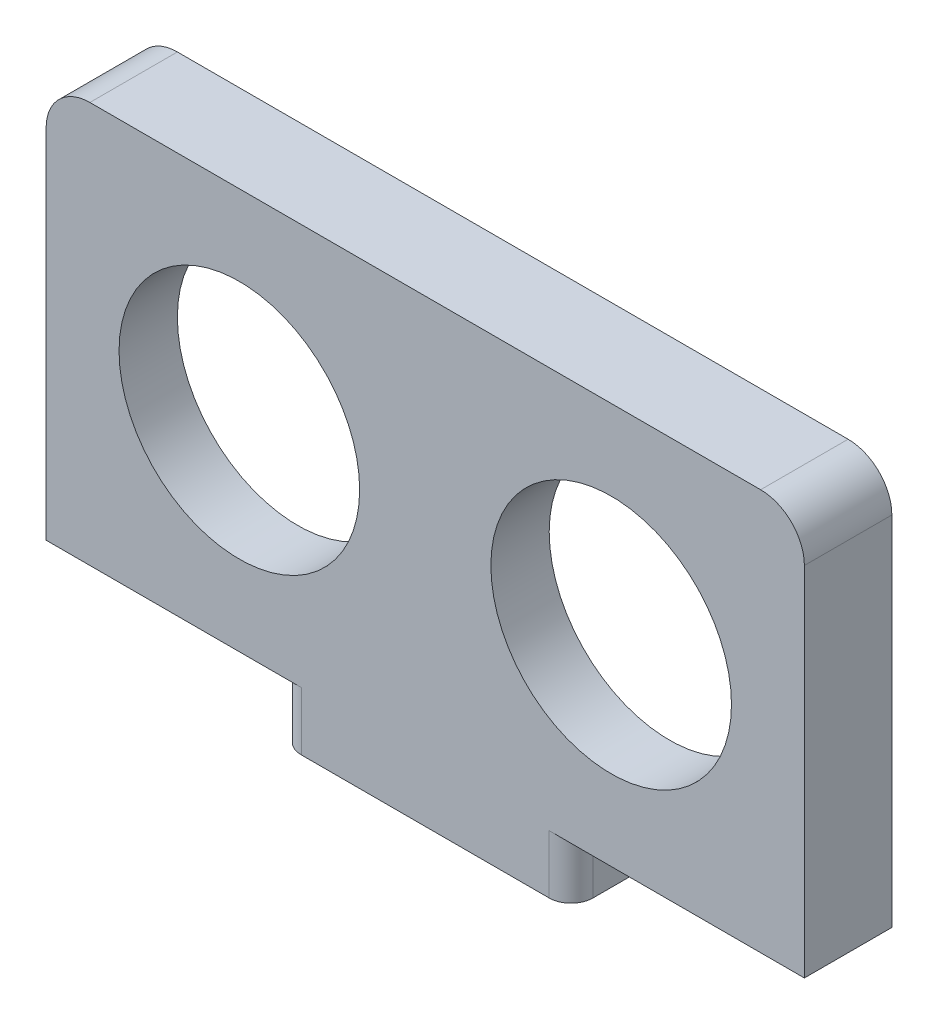
SolidWorks part; units mm, degrees
ref_plane "Спереди" through (0, 0, 0) normal (0, 0, 1) x (1, 0, 0)
ref_plane "Сверху" through (0, 0, 0) normal (0, 1, 0) x (1, 0, 0)
ref_plane "Справа" through (0, 0, 0) normal (1, 0, 0) x (0, 0, -1)
sketch "Эскиз1" plane through (0, 0, 0) normal (0, 0, 1) x (1, 0, 0)
  line L0 (-12.75, 0) -> (12.75, 0) construction
  line L1 (-5.5, -10.75) -> (-5.5, -5.75)
  line L2 (23, -10.75) -> (-23, -10.75)
  line L3 (23, -10.75) -> (23, 10.75)
  line L4 (23, 10.75) -> (-23, 10.75)
  line L5 (-23, -10.75) -> (-23, 10.75)
  line L6 (23, -10.75) -> (-23, 10.75) construction
  line L7 (23, 10.75) -> (-23, -10.75) construction
  line L8 (-4.5, -4.75) -> (4.5, -4.75)
  line L9 (5.5, -5.75) -> (5.5, -10.75)
  line L10 (0, -4.75) -> (0, 0) construction
  line L11 (-4.5, 0) -> (-4.5, -13.0183) construction
  line L12 (26, 13.75) -> (-26, 13.75)
  line L13 (-26, -13.75) -> (-26, 13.75)
  line L14 (26, -13.75) -> (-26, -13.75)
  line L15 (26, -13.75) -> (26, 13.75)
  line L16 (5.5, 5.75) -> (5.5, 10.75)
  line L17 (-4.5, 4.75) -> (4.5, 4.75)
  line L18 (-5.5, 10.75) -> (-5.5, 5.75)
  circle A0 centre (-12.75, 0) radius 8.25
  circle A1 centre (12.75, 0) radius 8.25
  arc A2 (4.5, -4.75) -> (5.5, -5.75) centre (4.5, -5.75) cw
  arc A3 (-5.5, -5.75) -> (-4.5, -4.75) centre (-4.5, -5.75) cw
  arc A4 (4.5, 4.75) -> (5.5, 5.75) centre (4.5, 5.75) ccw
  arc A5 (-5.5, 5.75) -> (-4.5, 4.75) centre (-4.5, 5.75) ccw
  point P5 (0, 0)
  dimension "D1" = 16.5
  dimension "D2" = 42
  dimension "D8" = 1
  dimension "D3" = 46
  dimension "D4" = 21.5
  dimension "D5" = 1
  dimension "D6" = 6
  dimension "D7" = 3
extrude "Бобышка-Вытянуть1" add sketch "Эскиз1" along normal blind 4 contours L14 L13 L12 L15 | A0 | A1
extrude "Бобышка-Вытянуть2" add sketch "Эскиз1<3>" against normal blind 2 contours L14 L15 L12 L13 L2 L5 L4 L3 region at (25.4118, 0, 0)
sketch "Эскиз1<3>" plane through (0, 0, 0) normal (0, 0, 1) x (1, 0, 0) same geometry as "Эскиз1"
extrude "Вырез-Вытянуть1" cut sketch "Эскиз1<4>" along normal blind 3 contours L18 A5 L17 A4 L16 L4 | A3 L1 L2 L9 A2 L8 region at (0, -7.7682, 0) region at (0, 7.7682, 0)
sketch "Эскиз1<4>" plane through (0, 0, 0) normal (0, 0, 1) x (1, 0, 0) same geometry as "Эскиз1"
fillet "Скругление1" radius 3 2 edges at (-26, 13.75, 1) (26, 13.75, 1)
sketch "Эскиз2" plane through (0, -13.75, 0) normal (0, -1, 0) x (1, 0, 0)
  line L0 (26, 4) -> (-26, 4) construction
  line L1 (-10, 4) -> (10, 4)
  line L2 (-10, 4) -> (-10, -2)
  line L3 (-10, -2) -> (10, -2)
  line L4 (10, 4) -> (10, -2)
  line L5 (26, -2) -> (-26, -2) construction
  line L6 (0, 4) -> (0, -2) construction
  dimension "D1" = 20
extrude "Бобышка-Вытянуть3" add sketch "Эскиз2" along normal blind 4 contours L2 L3 L4 L1
fillet "Скругление2" radius 1.5 4 edges
sketch "Эскиз3" plane through (0, 0, 4) normal (0, 0, 1) x (1, 0, 0)
  line L0 (0, -17.75) -> (0, -13.75) construction
  line L1 (-8.5, -17.75) -> (8.5, -17.75) construction
  line L2 (-8.5, -13.75) -> (8.5, -13.75) construction
  circle A0 centre (0, -15.75) radius 0.75
  dimension "D1" = 1.5
  dimension "D2" = 2
extrude "Вырез-Вытянуть2" [suppressed] cut sketch "Эскиз3" against normal through all contours A0
